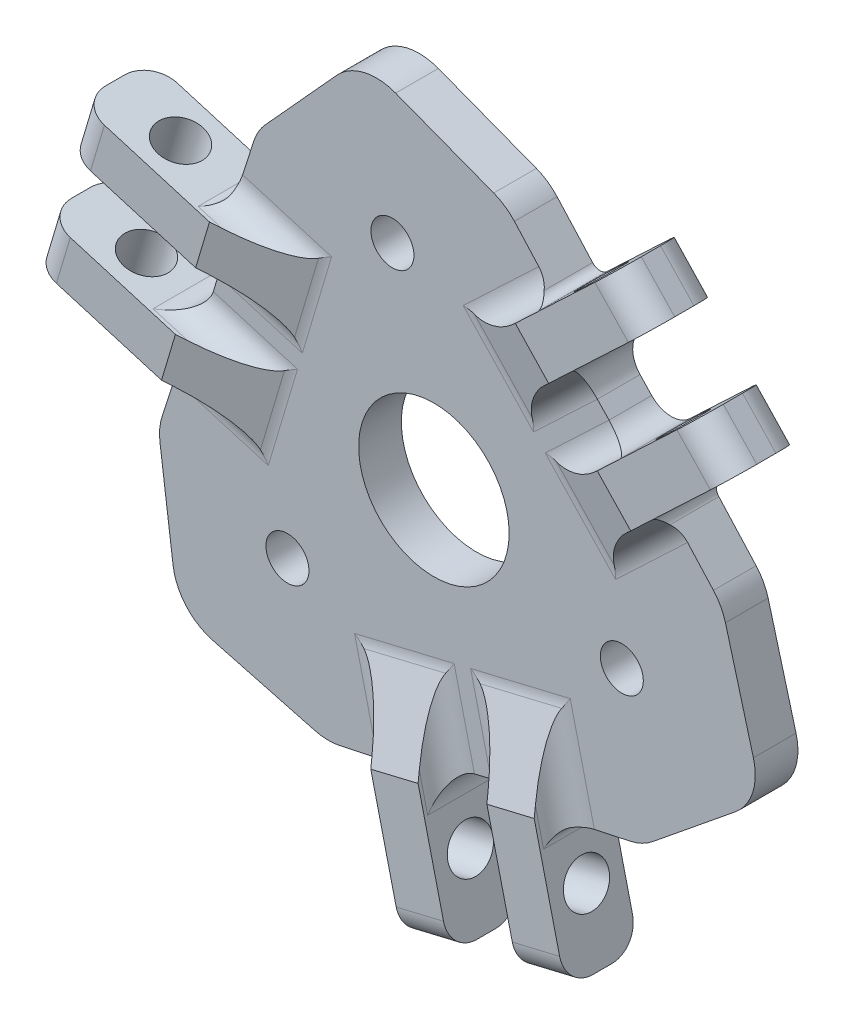
SolidWorks part; units mm, degrees
note: The reader was unsure of these and kept them because the rebuilt part matched: shared geometry of "Sketch4<2>".
ref_plane "Front" through (0, 0, 0) normal (0, 0, 1) x (1, 0, 0)
ref_plane "Top" through (0, 0, 0) normal (0, 1, 0) x (1, 0, 0)
ref_plane "Right" through (0, 0, 0) normal (1, 0, 0) x (0, 0, -1)
sketch "Sketch1" plane through (0, 0, 0) normal (0, 0, 1) x (1, 0, 0)
  line L9 (15.3473, 31.211) -> (8.0515, 33.9989)
  line L10 (3.6638, 32.953) -> (-1.6531, 27.1039)
  line L11 (-2.5002, 25.6411) -> (-9.3254, 4.4787)
  line L12 (-9.4846, 2.7307) -> (-8.5074, -4.7187)
  line L13 (-5.5657, -8.0651) -> (2.031, -10.0776)
  line L14 (3.8955, -10.1217) -> (25.4851, -5.4837)
  line L15 (27.1669, -4.6777) -> (33.3296, 0.3283)
  line L16 (34.6684, 4.4793) -> (32.5917, 12.1426)
  line L17 (31.6977, 13.7794) -> (16.8863, 30.1575)
  line L27 (15.3473, 31.211) -> (8.0515, 33.9989)
  line L28 (3.6638, 32.953) -> (-1.6531, 27.1039)
  line L29 (-2.5002, 25.6411) -> (-9.3254, 4.4787)
  line L30 (-9.4846, 2.7307) -> (-8.5074, -4.7187)
  line L31 (-5.5657, -8.0651) -> (2.031, -10.0776)
  line L32 (3.8955, -10.1217) -> (25.4851, -5.4837)
  line L33 (27.1669, -4.6777) -> (33.3296, 0.3283)
  line L34 (34.6684, 4.4793) -> (32.5917, 12.1426)
  line L35 (31.6977, 13.7794) -> (16.8863, 30.1575)
  circle A0 centre (24.8798, 5.3449) radius 1.6 construction
  circle A1 centre (7.8111, 24.219) radius 1.6 construction
  circle A2 centre (0, 0) radius 1.6 construction
  circle A3 centre (24.8798, 5.3449) radius 1.6
  circle A4 centre (7.8111, 24.219) radius 1.6
  circle A5 centre (0, 0) radius 1.6
  circle A6 centre (10.897, 9.8546) radius 25.6921 construction
  arc A17 (8.0515, 33.9989) -> (3.6638, 32.953) centre (6.6237, 30.2624) ccw
  circle A27 centre (10.897, 9.8546) radius 5.6
  arc A28 (-1.6531, 27.1039) -> (-2.5002, 25.6411) centre (1.3067, 24.4133) ccw
  arc A29 (-9.3254, 4.4787) -> (-9.4846, 2.7307) centre (-5.5185, 3.2509) ccw
  arc A30 (-8.5074, -4.7187) -> (-5.5657, -8.0651) centre (-4.5414, -4.1985) ccw
  arc A31 (2.031, -10.0776) -> (3.8955, -10.1217) centre (3.0553, -6.211) ccw
  arc A32 (25.4851, -5.4837) -> (27.1669, -4.6777) centre (24.6449, -1.5729) ccw
  arc A33 (33.3296, 0.3283) -> (34.6684, 4.4793) centre (30.8076, 3.4331) ccw
  arc A34 (32.5917, 12.1426) -> (31.6977, 13.7794) centre (28.731, 11.0964) ccw
  arc A35 (16.8863, 30.1575) -> (15.3473, 31.211) centre (13.9195, 27.4745) ccw
  arc A36 (8.0515, 33.9989) -> (3.6638, 32.953) centre (6.6237, 30.2624) ccw
  arc A37 (-1.6531, 27.1039) -> (-2.5002, 25.6411) centre (1.3067, 24.4133) ccw
  arc A38 (-9.3254, 4.4787) -> (-9.4846, 2.7307) centre (-5.5185, 3.2509) ccw
  arc A39 (-8.5074, -4.7187) -> (-5.5657, -8.0651) centre (-4.5414, -4.1985) ccw
  arc A40 (2.031, -10.0776) -> (3.8955, -10.1217) centre (3.0553, -6.211) ccw
  arc A41 (25.4851, -5.4837) -> (27.1669, -4.6777) centre (24.6449, -1.5729) ccw
  arc A42 (33.3296, 0.3283) -> (34.6684, 4.4793) centre (30.8076, 3.4331) ccw
  arc A43 (32.5917, 12.1426) -> (31.6977, 13.7794) centre (28.731, 11.0964) ccw
  arc A44 (16.8863, 30.1575) -> (15.3473, 31.211) centre (13.9195, 27.4745) ccw
  dimension "D2" = 11.2
  dimension "D1" = 0
extrude "Boss-Extrude1" add sketch "Sketch1" along normal blind 3.175
ref_plane "Plane1" through (0.4496, -0.4753, 0) normal (0.6872, -0.7265, 0) x (-0.7265, -0.6872, 0)
sketch "Sketch4" plane through (0.4496, -0.4753, 0) normal (0.6872, -0.7265, 0) x (-0.7265, -0.6872, 0)
  line L0 (-31.7213, 0) -> (-31.7213, -3.175)
  line L1 (-31.7213, -5.425) -> (-41.8813, -5.425)
  line L2 (-41.8813, -5.425) -> (-41.8813, 0)
  line L3 (-41.8813, 0) -> (-31.7213, 0)
  line L4 (-32.9913, -3.175) -> (-32.9913, 0) construction
  line L6 (-32.9913, 0) -> (-41.8813, 0) construction
  line L7 (-32.9913, 0) -> (-32.9913, -5.425) construction
  line L8 (-32.9913, -5.425) -> (-41.8813, -5.425) construction
  line L9 (-41.8813, 0) -> (-41.8813, -5.425) construction
  line L10 (-36.8013, 0) -> (-36.8013, -5.425) construction
  line L11 (-31.7213, -5.425) -> (-25.5395, -3.175)
  line L12 (-25.5395, -3.175) -> (-31.7213, -3.175)
  line L13 (-32.5973, 0) -> (-32.9923, 0) construction
  line L14 (-32.4968, -3.175) -> (-32.0216, -3.175) construction
  circle A0 centre (-36.8013, -2.7125) radius 1.675
  point P11 (-32.9913, -2.7125)
  dimension "D1" = 3.35
  dimension "D4" = 2.25
  dimension "D2" = 3.81
  dimension "D3" = 1.27
  dimension "D5" = 20
extrude "Boss-Extrude3" add sketch "Sketch4" along normal mid plane 12.5
extrude "Cut-Extrude2" cut sketch "Sketch4<2>" against normal mid plane 5.2625
sketch "Sketch4<2>" plane through (0.4496, -0.4753, 0) normal (0.6872, -0.7265, 0) x (-0.7265, -0.6872, 0) same geometry as "Sketch4"
fillet "Fillet1" radius 2 6 edges at (19.441, 21.1106, 3.175) (23.0573, 17.2875, 3.175) (25.8653, 14.9624, 3.175) (22.0552, 13.849, 3.175) (17.3772, 24.1397, 3.175) (15.9521, 20.3011, 3.175)
fillet "Fillet2" radius 2 2 edges at (25.3028, 19.4115, 2.5875) (21.6865, 23.2346, 2.5875)
fillet "Fillet3" radius 2 4 edges at (27.8241, 31.5309, 0) (33.9272, 25.0788, 0) (33.9272, 25.0788, 5.425) (27.8241, 31.5309, 5.425)
pattern_circular "CirPattern2" count 3 over 360 about axis through (10.897, 9.8546, 0) along (0, 0, 1) of "Cut-Extrude2", "Boss-Extrude3", "Fillet1", "Fillet3", "Fillet2"
fillet "Fillet5" radius 0.75 6 edges at (28.4321, 17.3904, 2.5875) (20.0457, 26.6638, 2.5875) (-3.9518, 21.1401, 2.5875) (-7.7897, 9.2405, 2.5875) (20.8798, -6.473, 2.5875) (8.6555, -9.0991, 2.5875)
